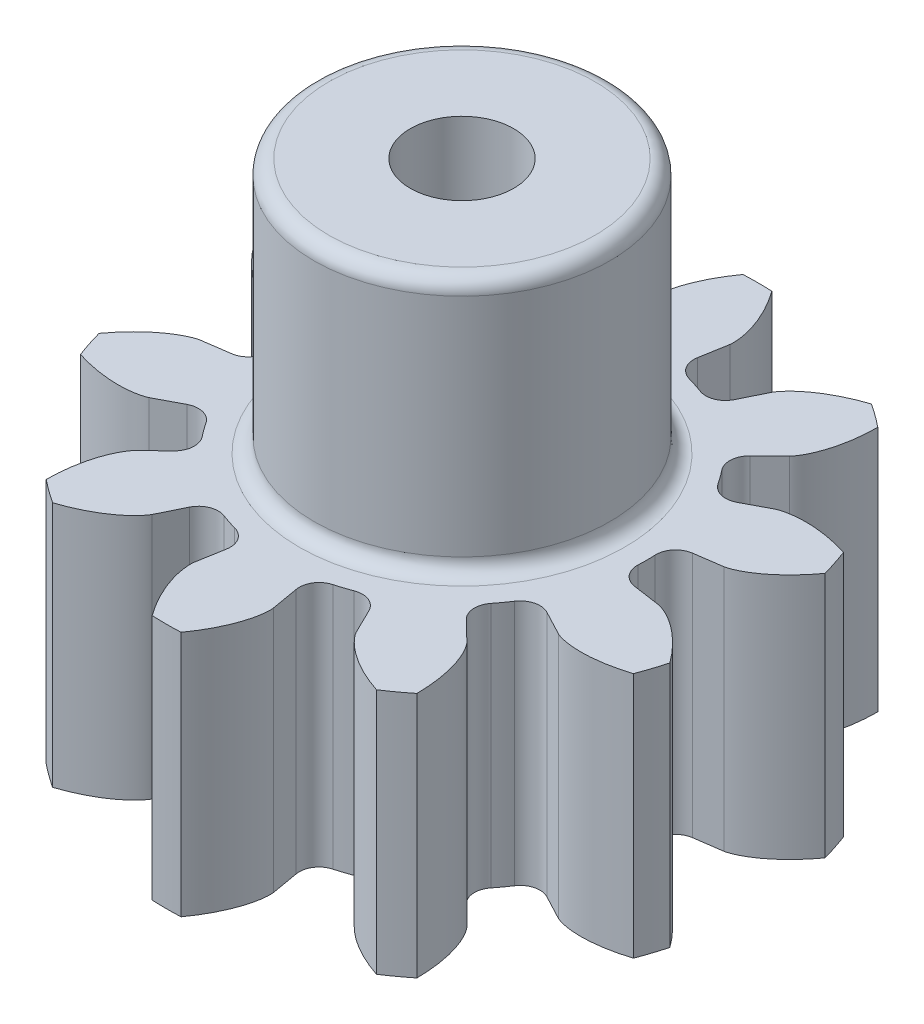
SolidWorks part; units mm, degrees
ref_plane "Front Plane" through (0, 0, 0) normal (0, 0, 1) x (1, 0, 0)
ref_plane "Top Plane" through (0, 0, 0) normal (0, 1, 0) x (1, 0, 0)
ref_plane "Right Plane" through (0, 0, 0) normal (1, 0, 0) x (0, 0, -1)
sketch "Sketch2" plane through (0, 0, 0) normal (0, 1, 0) x (1, 0, 0)
  circle A0 centre (0, 0) radius 15.24
  dimension "D1" = 30.48
extrude "Boss-Extrude1" add sketch "Sketch2" along normal blind 12.7
sketch "Sketch3" plane through (0, 0, 0) normal (0, -1, 0) x (-1, 0, 0)
  line L0 (0, 0) -> (11.8137, -1.691) construction
  line L1 (0, 0) -> (11.8137, 1.691) construction
  line L2 (11.8137, -1.691) -> (9.4289, -1.3497)
  line L3 (11.8137, 1.691) -> (9.4289, 1.3497)
  circle A0 centre (0, 0) radius 15.24
  circle A1 centre (0, 0) radius 12.7
  circle A2 centre (0, 0) radius 11.938
  circle A3 centre (0, 0) radius 9.525
  arc A4 (14.7073, 3.9942) -> (14.7073, -3.9942) centre (0, 0) cw
  arc A5 (9.4289, 1.3497) -> (9.4289, -1.3497) centre (0, 0) cw
  spline S0 degree 4 poles (11.8137, 1.691) (11.8192, 1.6919) (11.8345, 1.6947) (11.8634, 1.701) (11.9102, 1.7129) (11.9692, 1.7305) (12.0448, 1.7558) (12.1329, 1.789) (12.2286, 1.829) (12.3315, 1.8763) (12.433, 1.9267) (12.5329, 1.9801) (12.6314, 2.036) (12.7494, 2.1069) (12.8888, 2.1963) (13.0487, 2.3071) (13.2263, 2.4402) (13.4031, 2.5835) (13.5735, 2.7307) (13.7413, 2.8866) (13.9005, 3.0423) (14.0612, 3.2111) (14.2071, 3.3705) (14.3651, 3.5565) (14.4911, 3.7088) (14.6511, 3.9175) (14.7439, 4.0431) (14.8502, 4.1926) (14.8963, 4.2604) (14.9247, 4.3021) knots 0 0 0 0 0 0.005377 0.015084 0.028532 0.04661 0.064855 0.092111 0.119476 0.146842 0.174209 0.201575 0.228941 0.256307 0.307035 0.361767 0.4165 0.471232 0.525964 0.580697 0.635429 0.690161 0.744894 0.799626 0.854358 0.909091 0.954545 1 1 1 1 1 construction
  spline S1 degree 4 poles (11.8137, 1.691) (11.8192, 1.6919) (11.8345, 1.6947) (11.8634, 1.701) (11.9102, 1.7129) (11.9692, 1.7305) (12.0448, 1.7558) (12.1329, 1.789) (12.2286, 1.829) (12.3315, 1.8763) (12.433, 1.9267) (12.5329, 1.9801) (12.6314, 2.036) (12.7494, 2.1069) (12.8888, 2.1963) (13.0487, 2.3071) (13.2263, 2.4402) (13.4031, 2.5835) (13.5735, 2.7307) (13.7413, 2.8866) (13.9005, 3.0423) (14.0612, 3.2111) (14.2071, 3.3705) (14.3651, 3.5565) (14.4911, 3.7088) (14.6164, 3.8723) (14.6768, 3.9527) (14.7073, 3.9942) knots 0 0 0 0 0 0.005377 0.015084 0.028532 0.04661 0.064855 0.092111 0.119476 0.146842 0.174209 0.201575 0.228941 0.256307 0.307035 0.361767 0.4165 0.471232 0.525964 0.580697 0.635429 0.690161 0.744894 0.799626 0.854358 0.909091 0.909091 0.909091 0.909091 0.909091
  spline S2 degree 4 poles (11.8137, -1.691) (11.8192, -1.6919) (11.8345, -1.6947) (11.8634, -1.701) (11.9102, -1.7129) (11.9692, -1.7305) (12.0448, -1.7558) (12.1329, -1.789) (12.2286, -1.829) (12.3315, -1.8763) (12.433, -1.9267) (12.5329, -1.9801) (12.6314, -2.036) (12.7494, -2.1069) (12.8888, -2.1963) (13.0487, -2.3071) (13.2263, -2.4402) (13.4031, -2.5835) (13.5735, -2.7307) (13.7413, -2.8866) (13.9005, -3.0423) (14.0612, -3.2111) (14.2071, -3.3705) (14.3651, -3.5565) (14.4911, -3.7088) (14.6511, -3.9175) (14.7439, -4.0431) (14.8502, -4.1926) (14.8963, -4.2604) (14.9247, -4.3021) knots 0 0 0 0 0 0.005377 0.015084 0.028532 0.04661 0.064855 0.092111 0.119476 0.146842 0.174209 0.201575 0.228941 0.256307 0.307035 0.361767 0.4165 0.471232 0.525964 0.580697 0.635429 0.690161 0.744894 0.799626 0.854358 0.909091 0.954545 1 1 1 1 1 construction
  spline S3 degree 4 poles (11.8137, -1.691) (11.8192, -1.6919) (11.8345, -1.6947) (11.8634, -1.701) (11.9102, -1.7129) (11.9692, -1.7305) (12.0448, -1.7558) (12.1329, -1.789) (12.2286, -1.829) (12.3315, -1.8763) (12.433, -1.9267) (12.5329, -1.9801) (12.6314, -2.036) (12.7494, -2.1069) (12.8888, -2.1963) (13.0487, -2.3071) (13.2263, -2.4402) (13.4031, -2.5835) (13.5735, -2.7307) (13.7413, -2.8866) (13.9005, -3.0423) (14.0612, -3.2111) (14.2071, -3.3705) (14.3651, -3.5565) (14.4911, -3.7088) (14.6164, -3.8723) (14.6768, -3.9527) (14.7073, -3.9942) knots 0 0 0 0 0 0.005377 0.015084 0.028532 0.04661 0.064855 0.092111 0.119476 0.146842 0.174209 0.201575 0.228941 0.256307 0.307035 0.361767 0.4165 0.471232 0.525964 0.580697 0.635429 0.690161 0.744894 0.799626 0.854358 0.909091 0.909091 0.909091 0.909091 0.909091
  circle M5 centre (0, 0) radius 15.24
  dimension "D1" = 30.48
  dimension "D2" = 25.4
  dimension "D3" = 23.876
  dimension "D4" = 19.05
extrude "Cut-Extrude1" cut sketch "Sketch3" against normal through all contours A1 S3 S1 M5 | A2 S3 A1 S1 | L2 S3 A2 S1 L3 A3 region at (-10.7404, 0, 0) region at (-12.2842, 0, 0) region at (-14.0094, 0, 0)
fillet "Fillet1" radius 1.016 2 edges at (-9.4289, 6.35, -1.3497) (-9.4289, 6.35, 1.3497)
pattern_circular "CirPattern1" count 10 over 360 about axis through (0, 0, 0) along (0, 1, 0) of "Fillet1", "Cut-Extrude1"
sketch "Sketch4" plane through (0, 12.7, 0) normal (0, 1, 0) x (1, 0, 0)
  circle A1 centre (0, 0) radius 7.62
  dimension "D2" = 15.24
extrude "Boss-Extrude2" add sketch "Sketch4" along normal blind 13.16
sketch "Sketch5" plane through (0, 25.86, 0) normal (0, 1, 0) x (1, 0, 0)
  circle A0 centre (0, 0) radius 2.667
  dimension "D1" = 5.334
extrude "Cut-Extrude2" cut sketch "Sketch5" against normal through all
fillet "Fillet2" radius 0.762 2 edges at (0, 25.86, 7.62) (0, 12.7, 7.62)
equation "\"DiametralPitch\"= 10"
equation "\"NumTeeth\"= 10"
equation "\"PressureAngle\"= 20deg"
equation "\"Addendum\"= 1 / \"DiametralPitch\""
equation "\"Dedendum\"= 1.25 / \"DiametralPitch\""
equation "\"WorkingDepth\"= 2 / \"DiametralPitch\""
equation "\"WholeDepth\"= 2.25 / \"DiametralPitch\""
equation "\"Clearance\"= 0.3 / \"DiametralPitch\""
equation "\"ToothThickness\"= 1.5708 / \"DiametralPitch\""
equation "\"CircularPitch\"= pi / \"DiametralPitch\""
equation "\"PitchCircle\"= \"NumTeeth\" / \"DiametralPitch\""
equation "\"OutsideDiameter\"= ( \"NumTeeth\" + 2 ) / \"DiametralPitch\""
equation "\"Fillet\"= \"Clearance\" * cos ( \"PressureAngle\" ) * tan ( ( 90 + \"PressureAngle\" ) / 2 )"
equation "\"AddendumCircle\"= \"PitchCircle\" + ( 2 * \"Addendum\" )"
equation "\"DedendumCircle\"= \"PitchCircle\" - ( 2 * \"Dedendum\" )"
equation "\"BaseCircle\"= \"PitchCircle\" * cos ( \"PressureAngle\" )"
equation "\"PitchAngle\"= 360deg / \"NumTeeth\""
equation "\"Alpha\"= sqr ( \"PitchCircle\" ^ 2 - \"BaseCircle\" ^ 2 ) / \"BaseCircle\" * 180 / PI - \"PressureAngle\""
equation "\"Beta\"= ( \"PitchAngle\" / 4 - \"Alpha\" )"
equation "\"Phi\"= sqr ( ( \"AddendumCircle\" / 2 ) ^ 2 - ( \"BaseCircle\" / 2 ) ^ 2 ) / ( \"BaseCircle\" / 2 )"
